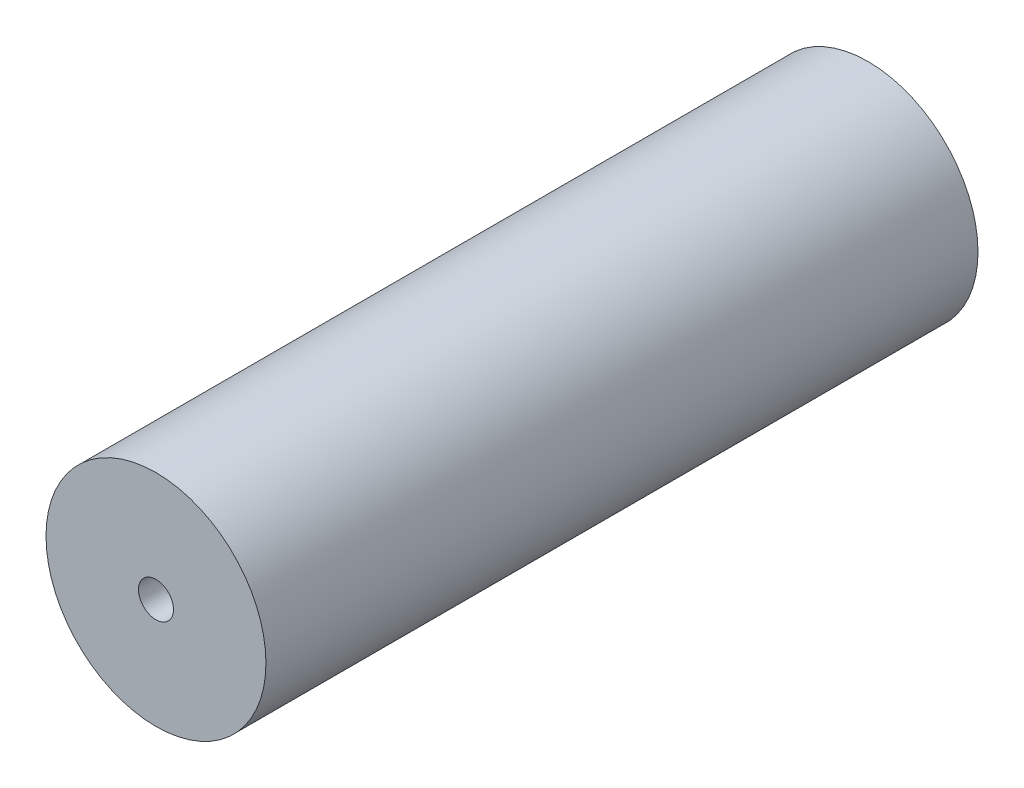
SolidWorks part; units mm, degrees
material "6061-T6 (SS)"
ref_plane "Front Plane" through (0, 0, 0) normal (0, 0, 1) x (1, 0, 0)
ref_plane "Top Plane" through (0, 0, 0) normal (0, 1, 0) x (1, 0, 0)
ref_plane "Right Plane" through (0, 0, 0) normal (1, 0, 0) x (0, 0, -1)
sketch "Sketch1" plane through (0, 0, 0) normal (0, 0, 1) x (1, 0, 0)
  circle A0 centre (0, 0) radius 12.7
  circle A1 centre (0, 0) radius 2.0193
  dimension "D1" = 25.4
  dimension "D2" = 4.0386
extrude "Boss-Extrude1" add sketch "Sketch1" along normal blind 82.2325
hole_wizard "#10-32 Tapped Hole1" positions "3DSketch1" profile "Sketch5" tap size "#10-32" standard "ANSI Inch" end condition through all
sketch3d "3DSketch1"
  line L0 (0, 0, 82.2325) -> (0, 0, 0) construction
  point P0 (0, 0, 82.2325)
sketch "Sketch5" plane through (0, 0, 82.2325) normal (1, 0, 0) x (0, -1, 0)
  line L0 (0, 0) -> (0, 82.2325)
  line L1 (0, 82.2325) -> (2.0193, 82.2325)
  line L2 (2.0193, 82.2325) -> (2.0193, 0)
  line L5 (2.0193, 0) -> (0, 0)
  line L11 (0, -6.35) -> (0, 107.95) construction
  dimension "Thru Tap Drill Dia." = 4.0386
  dimension "Thru Tap Drill Depth" = 82.2325
cosmetic thread "Hole Thread1" parameters "D2"=4.826
hole_wizard "#10-32 Tapped Hole2" positions "3DSketch2" profile "Sketch6" tap size "#10-32" standard "ANSI Inch" end condition through all
sketch3d "3DSketch2"
  point P0 (0, 0, 0)
sketch "Sketch6" plane through (0, 0, 0) normal (1, 0, 0) x (0, 1, 0)
  line L0 (0, 0) -> (0, 82.2325)
  line L1 (0, 82.2325) -> (2.0193, 82.2325)
  line L2 (2.0193, 82.2325) -> (2.0193, 0)
  line L5 (2.0193, 0) -> (0, 0)
  line L11 (0, -6.35) -> (0, 107.95) construction
  dimension "Thru Tap Drill Dia." = 4.0386
  dimension "Thru Tap Drill Depth" = 82.2325
cosmetic thread "Hole Thread2" parameters "D2"=4.826
